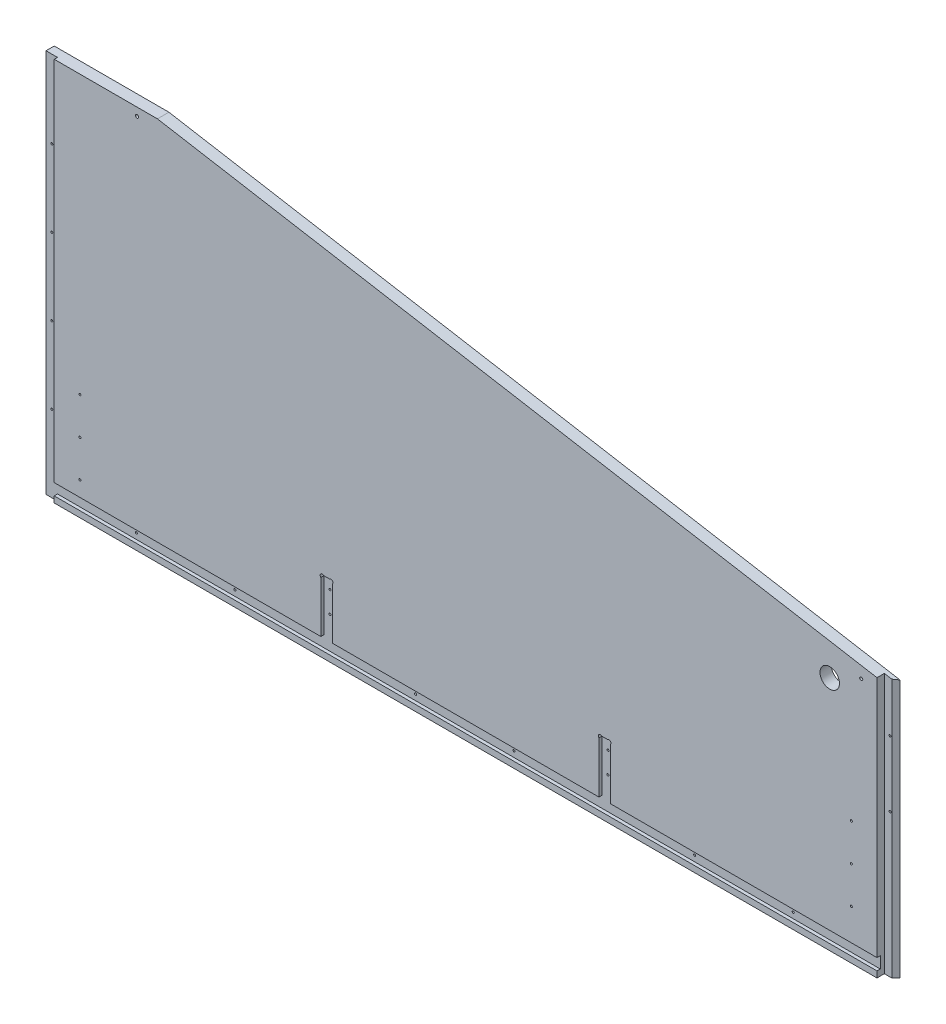
SolidWorks part; units mm, degrees
material "Maple"
ref_plane "Front Plane" through (0, 0, 0) normal (0, 0, 1) x (1, 0, 0)
ref_plane "Top Plane" through (0, 0, 0) normal (0, 1, 0) x (1, 0, 0)
ref_plane "Right Plane" through (0, 0, 0) normal (1, 0, 0) x (0, 0, -1)
sketch "Sketch1" plane through (0, 0, 0) normal (0, 0, 1) x (1, 0, 0)
  line L0 (8932.6508, -5243.5125) -> (10226.1458, -5243.5125)
  line L1 (9086.3208, -4722.0918) -> (10222.9708, -4853.7812)
  line L2 (8914.8708, -6342.0625) -> (10197.5708, -6342.0625)
  line L3 (8914.8708, -5808.6625) -> (10197.5708, -5808.6625)
  line L4 (8919.6333, -5253.0375) -> (10218.2083, -5253.0375)
  line L5 (9134.2633, -4656.1375) -> (9134.2633, -4638.3575)
  line L6 (9091.0833, -4638.3575) -> (9134.2633, -4638.3575)
  line L7 (9091.0833, -4567.2375) -> (9091.0833, -4638.3575)
  line L8 (9134.2633, -4656.1375) -> (9581.3033, -4656.1375)
  line L9 (9091.0833, -4567.2375) -> (9624.4833, -4567.2375)
  line L10 (9581.3033, -4656.1375) -> (9581.3033, -4638.3575)
  line L11 (9581.3033, -4638.3575) -> (9624.4833, -4638.3575)
  line L12 (9624.4833, -4567.2375) -> (9624.4833, -4638.3575)
  line L13 (8932.6508, -5225.7325) -> (9344.9775, -5225.7325)
  line L14 (8932.6508, -5256.2125) -> (8932.6508, -5243.5125)
  line L15 (8911.6958, -5256.2125) -> (8932.6508, -5256.2125)
  line L16 (8914.8708, -4722.0918) -> (9086.3208, -4722.0918)
  line L17 (8911.6958, -4715.5913) -> (8932.6508, -4715.5913)
  line L18 (8914.8708, -6342.0625) -> (8914.8708, -5808.6625)
  line L19 (12082.9917, -4722.0918) -> (10946.3417, -4853.7812)
  line L20 (12236.6617, -5243.5125) -> (10943.1667, -5243.5125)
  line L21 (10951.1042, -5253.0375) -> (12249.6792, -5253.0375)
  line L22 (10838.3917, -5656.2625) -> (11308.2917, -5656.2625)
  line L23 (10838.3917, -5719.7625) -> (11308.2917, -5719.7625)
  line L24 (10838.3917, -5742.5368) -> (11308.2917, -5742.5368)
  line L25 (10806.6417, -6342.0625) -> (11340.0417, -6342.0625)
  line L26 (10803.4667, -6335.7125) -> (11343.2167, -6335.7125)
  line L27 (10803.4667, -6317.9325) -> (11343.2167, -6317.9325)
  line L28 (10943.1667, -5225.7325) -> (11376.4483, -5225.7325)
  line L29 (11506.7292, -4754.5625) -> (10806.6417, -4827.5875)
  line L30 (11506.7292, -4567.2375) -> (11506.7292, -4754.5625)
  line L31 (10806.6417, -4567.2375) -> (10806.6417, -4827.5875)
  line L32 (10806.6417, -4567.2375) -> (11506.7292, -4567.2375)
  line L33 (10235.6708, -6329.3625) -> (10245.1958, -6329.3625)
  line L34 (10245.1958, -6329.3625) -> (10254.7208, -6278.5625)
  line L35 (10302.3458, -6329.3625) -> (10311.8708, -6278.5625)
  line L36 (10302.3458, -6329.3625) -> (10292.8208, -6329.3625)
  line L37 (10245.1958, -5821.3625) -> (10254.7208, -5872.1625)
  line L38 (10235.6708, -5821.3625) -> (10245.1958, -5821.3625)
  line L39 (10292.8208, -5821.3625) -> (10302.3458, -5821.3625)
  line L40 (10302.3458, -5821.3625) -> (10311.8708, -5872.1625)
  line L41 (10235.6708, -5821.3625) -> (10235.6708, -6329.3625)
  line L42 (10254.7208, -5872.1625) -> (10254.7208, -6278.5625)
  line L43 (10311.8708, -5872.1625) -> (10311.8708, -6278.5625)
  line L44 (10292.8208, -5821.3625) -> (10292.8208, -6329.3625)
  line L45 (8932.6508, -5225.7325) -> (8932.6508, -4715.5913)
  line L46 (8911.6958, -4715.5913) -> (8911.6958, -5256.2125)
  line L47 (8914.8708, -5248.275) -> (8914.8708, -4722.0918)
  line L48 (8919.6333, -5253.0375) -> (8914.8708, -5248.275)
  line L49 (8914.8708, -5145.0875) -> (8937.426, -5145.0875)
  line L50 (8914.8708, -5202.2375) -> (8937.426, -5202.2375)
  line L51 (10838.3917, -5656.2625) -> (10838.3917, -5719.7625)
  line L52 (10832.0417, -5736.1868) -> (10856.1717, -5736.1868)
  line L53 (10806.6417, -6342.0625) -> (10806.6417, -5818.7368)
  line L54 (10832.0417, -5649.9125) -> (10856.1717, -5649.9125)
  line L55 (10832.0417, -5726.1125) -> (10856.1717, -5726.1125)
  line L56 (10806.6417, -5818.7368) -> (10833.9015, -5818.7368)
  line L57 (10832.0417, -5806.0442) -> (10851.6815, -5806.0442)
  line L58 (10856.1717, -5801.5541) -> (10856.1717, -5736.1868)
  line L59 (10838.3917, -5814.2467) -> (10838.3917, -5742.5368)
  line L60 (10832.0417, -5806.0442) -> (10832.0417, -5736.1868)
  line L61 (10803.4667, -6317.9325) -> (10803.4667, -6335.7125)
  line L62 (10197.5708, -5808.6625) -> (10197.5708, -6342.0625)
  line L63 (9762.3842, -6348.4125) -> (9762.3842, -5802.3125)
  line L64 (9780.1642, -6348.4125) -> (9762.3842, -6348.4125)
  line L65 (9780.1642, -5802.3125) -> (9780.1642, -6348.4125)
  line L66 (9762.3842, -5802.3125) -> (9780.1642, -5802.3125)
  line L67 (9332.2775, -6348.4125) -> (9332.2775, -5802.3125)
  line L68 (9332.2775, -6348.4125) -> (9350.0575, -6348.4125)
  line L69 (9350.0575, -5802.3125) -> (9350.0575, -6348.4125)
  line L70 (9332.2775, -5802.3125) -> (9350.0575, -5802.3125)
  line L71 (9993.8374, -6061.075) -> (9993.8374, -6045.2418)
  line L72 (9998.5999, -6065.8375) -> (10014.4331, -6065.8375)
  line L73 (9998.5999, -6084.8875) -> (10014.4331, -6084.8875)
  line L74 (9993.8374, -6105.4832) -> (9993.8374, -6089.65)
  line L75 (9974.7874, -6105.4832) -> (9974.7874, -6089.65)
  line L76 (9954.1917, -6084.8875) -> (9970.0249, -6084.8875)
  line L77 (9974.7874, -6061.075) -> (9974.7874, -6045.2418)
  line L78 (9954.1917, -6065.8375) -> (9970.0249, -6065.8375)
  line L79 (10793.9417, -6237.2875) -> (10816.4969, -6237.2875)
  line L80 (10793.9417, -6294.4375) -> (10816.4969, -6294.4375)
  line L81 (10856.1717, -5649.9125) -> (10856.1717, -5726.1125)
  line L82 (10832.0417, -5726.1125) -> (10832.0417, -5649.9125)
  line L83 (10226.1458, -5225.7325) -> (10226.1458, -5243.5125)
  line L84 (10205.1908, -5257.8) -> (10205.1908, -4844.2499)
  line L85 (10230.9083, -4844.2499) -> (10230.9083, -5257.8)
  line L86 (10205.1908, -5257.8) -> (10230.9083, -5257.8)
  line L87 (10205.1908, -4844.2499) -> (10230.9083, -4844.2499)
  line L88 (10946.3417, -5176.8375) -> (10968.8969, -5176.8375)
  line L89 (9349.4676, -5141.9125) -> (9358.2674, -5141.9125)
  line L90 (10946.3417, -5119.6875) -> (10968.8969, -5119.6875)
  line L91 (9929.011, -4660.9635) -> (10066.0807, -4660.9635)
  line L92 (9929.011, -4678.7435) -> (10066.0807, -4678.7435)
  line L93 (10943.1667, -5225.7325) -> (10943.1667, -5243.5125)
  line L94 (10946.3417, -5248.275) -> (10951.1042, -5253.0375)
  line L95 (10946.3417, -5257.8063) -> (10946.3417, -4849.0188)
  line L96 (10964.1217, -5257.8) -> (10964.1217, -4844.2499)
  line L97 (10938.4042, -4844.2499) -> (10938.4042, -5257.8)
  line L98 (10938.4042, -5257.8) -> (10964.1217, -5257.8)
  line L99 (10964.1217, -4844.2499) -> (10938.4042, -4844.2499)
  line L100 (10344.8908, -4560.8875) -> (10369.0208, -4560.8875)
  line L101 (10344.8908, -4560.8875) -> (10369.0208, -4560.8875)
  line L102 (10800.2917, -4560.8875) -> (10824.4217, -4560.8875)
  line L103 (10200.4156, -5119.6875) -> (10222.9708, -5119.6875)
  line L104 (10200.4156, -5176.8375) -> (10222.9708, -5176.8375)
  line L105 (9344.9775, -5146.4026) -> (9344.9775, -5225.7325)
  line L106 (10344.8908, -4560.8875) -> (10344.8908, -4833.9375)
  line L107 (9792.8642, -5225.7325) -> (9792.8642, -5146.4026)
  line L108 (9362.7575, -5225.7325) -> (9775.0842, -5225.7325)
  line L109 (9680.3633, -4761.8396) -> (9680.3633, -4559.9604)
  line L110 (9656.2333, -4559.9604) -> (9680.3633, -4559.9604)
  line L111 (9656.2333, -4761.8396) -> (9680.3633, -4761.8396)
  line L112 (9656.2333, -4761.8396) -> (9656.2333, -4559.9604)
  line L113 (9779.5743, -5141.9125) -> (9788.374, -5141.9125)
  line L114 (10070.5708, -4665.4536) -> (10070.5708, -4674.2534)
  line L115 (9924.5208, -4674.2534) -> (9924.5208, -4665.4536)
  line L116 (12127.4417, -6188.3925) -> (12205.5015, -6188.3925)
  line L117 (12209.9917, -6170.6125) -> (12209.9917, -6183.9024)
  line L118 (9792.8642, -5225.7325) -> (10226.1458, -5225.7325)
  line L119 (9662.5833, -4754.5625) -> (10362.6708, -4827.5875)
  line L120 (9662.5833, -4567.2375) -> (9662.5833, -4754.5625)
  line L121 (10362.6708, -4567.2375) -> (10362.6708, -4827.5875)
  line L122 (9662.5833, -4567.2375) -> (10362.6708, -4567.2375)
  line L123 (10824.4217, -4833.9375) -> (10800.2917, -4833.9375)
  line L124 (10800.2917, -4833.9375) -> (10800.2917, -4560.8875)
  line L125 (10824.4217, -4560.8875) -> (10824.4217, -4833.9375)
  line L126 (10344.8908, -4833.9375) -> (10369.0208, -4833.9375)
  line L127 (10369.0208, -4833.9375) -> (10369.0208, -4560.8875)
  line L128 (10222.9708, -5248.275) -> (10218.2083, -5253.0375)
  line L129 (10222.9708, -5257.8063) -> (10222.9708, -4849.0188)
  line L130 (11734.6544, -5701.375) -> (11739.2301, -5701.375)
  line L131 (9362.7575, -5225.7325) -> (9362.7575, -5146.4026)
  line L132 (9775.0842, -5146.4026) -> (9775.0842, -5225.7325)
  line L133 (11761.3864, -5701.375) -> (11756.8282, -5701.375)
  line L134 (11734.6544, -5693.755) -> (11739.2301, -5693.755)
  line L135 (11761.4039, -5693.755) -> (11756.8282, -5693.755)
  line L136 (11734.6544, -5701.375) -> (11739.2301, -5701.375)
  line L137 (11744.3462, -5721.3024) -> (11744.3462, -5706.4179)
  line L138 (11751.7122, -5721.3024) -> (11751.7122, -5706.4179)
  line L139 (11740.0917, -6170.6125) -> (11740.0917, -6183.9024)
  line L140 (11689.2917, -6188.3925) -> (11822.6417, -6188.3925)
  line L141 (11689.2917, -6348.4093) -> (11689.2917, -6164.2657)
  line L142 (11689.2917, -6164.2657) -> (11746.4417, -6164.2657)
  line L143 (11746.4417, -6164.2657) -> (11746.4417, -6188.3925)
  line L144 (11689.2917, -6164.2657) -> (11746.4417, -6164.2657)
  line L145 (11340.0417, -5818.7368) -> (11340.0417, -6342.0625)
  line L146 (11290.5117, -5726.1125) -> (11314.6417, -5726.1125)
  line L147 (11290.5117, -5649.9125) -> (11290.5117, -5726.1125)
  line L148 (11340.0417, -5818.7368) -> (11312.7818, -5818.7368)
  line L149 (11314.6417, -5806.0442) -> (11295.0018, -5806.0442)
  line L150 (11290.5117, -5801.5541) -> (11290.5117, -5736.1868)
  line L151 (11308.2917, -5814.2467) -> (11308.2917, -5742.5368)
  line L152 (11314.6417, -5806.0442) -> (11314.6417, -5736.1868)
  line L153 (11290.5117, -5736.1868) -> (11314.6417, -5736.1868)
  line L154 (11848.0417, -6267.1325) -> (11962.3417, -6267.1325)
  line L155 (11962.3417, -6267.1325) -> (11962.3417, -6203.6325)
  line L156 (11343.2167, -6317.9325) -> (11343.2167, -6335.7125)
  line L157 (11365.4417, -5656.2625) -> (11365.4417, -5719.7625)
  line L158 (11365.4417, -5656.2625) -> (11479.7417, -5656.2625)
  line L159 (11778.1917, -6071.3937) -> (11802.3217, -6071.3937)
  line L160 (11314.6417, -5726.1125) -> (11314.6417, -5649.9125)
  line L161 (11314.6417, -5649.9125) -> (11290.5117, -5649.9125)
  line L162 (11308.2917, -5719.7625) -> (11308.2917, -5656.2625)
  line L163 (11689.2917, -6348.4093) -> (11713.4217, -6348.4093)
  line L164 (12203.6417, -6164.2657) -> (12260.7917, -6164.2657)
  line L165 (11713.4217, -6348.4093) -> (11713.4217, -6164.2657)
  line L166 (11695.6417, -6342.0625) -> (11695.6417, -6170.6125)
  line L167 (11695.6417, -6048.5337) -> (11699.4517, -6052.3437)
  line L168 (11822.6417, -6292.5325) -> (11822.6417, -6188.3925)
  line L169 (11695.6417, -6342.0625) -> (11695.6417, -6170.6125)
  line L170 (11848.0417, -6203.6325) -> (11962.3417, -6203.6325)
  line L171 (11848.0417, -6203.6325) -> (11848.0417, -6267.1325)
  line L172 (11987.7417, -6267.1325) -> (11987.7417, -6203.6325)
  line L173 (11784.5417, -6077.7437) -> (11784.5417, -6141.2438)
  line L174 (11517.8417, -5656.2625) -> (11632.1417, -5656.2625)
  line L175 (11632.1417, -5656.2625) -> (11632.1417, -5719.7625)
  line L176 (11632.1417, -5719.7625) -> (11517.8417, -5719.7625)
  line L177 (11517.8417, -5719.7625) -> (11517.8417, -5656.2625)
  line L178 (11692.4667, -6028.2137) -> (11692.4667, -6045.9937)
  line L179 (11695.6417, -5979.3188) -> (11718.1969, -5979.3188)
  line L180 (11695.6417, -5922.1687) -> (11718.1969, -5922.1687)
  line L181 (11821.0415, -5722.9375) -> (11821.0415, -5943.6)
  line L182 (11687.7042, -5651.5) -> (11701.9917, -5651.5)
  line L183 (11687.7042, -5651.5) -> (11687.7042, -6055.5251)
  line L184 (11687.7042, -6055.5251) -> (11701.9917, -6055.5251)
  line L185 (11701.9917, -6055.5251) -> (11701.9917, -5651.5)
  line L186 (11695.6417, -6055.2013) -> (11695.6417, -5649.595)
  line L187 (11695.6417, -5656.2625) -> (11695.6417, -6048.5337)
  line L188 (11695.6417, -6170.6125) -> (11740.0917, -6170.6125)
  line L189 (12203.6417, -6164.2657) -> (12203.6417, -6188.3925)
  line L190 (12254.4417, -6342.0625) -> (12254.4417, -6170.6125)
  line L191 (12129.0419, -5943.6) -> (12129.0419, -5722.9375)
  line L192 (12254.4417, -6048.5337) -> (12250.6317, -6052.3437)
  line L193 (12257.6167, -6045.9937) -> (12257.6167, -6028.2137)
  line L194 (12248.0917, -5651.5) -> (12262.3792, -5651.5)
  line L195 (12262.3792, -5651.5) -> (12262.3792, -6055.5251)
  line L196 (12262.3792, -6055.5251) -> (12248.0917, -6055.5251)
  line L197 (12248.0917, -6055.5251) -> (12248.0917, -5651.5)
  line L198 (12254.4417, -6141.2438) -> (12254.4417, -6077.7437)
  line L199 (12236.6617, -6164.2657) -> (12260.7917, -6164.2657)
  line L200 (12102.0417, -6267.1325) -> (11987.7417, -6267.1325)
  line L201 (11330.1865, -6237.2875) -> (11352.7417, -6237.2875)
  line L202 (11330.1865, -6294.4375) -> (11352.7417, -6294.4375)
  line L203 (11474.6617, -5851.8425) -> (11492.4417, -5851.8425)
  line L204 (11474.6617, -5808.6625) -> (11474.6617, -5851.8425)
  line L205 (11403.5417, -5808.6625) -> (11474.6617, -5808.6625)
  line L206 (11492.4417, -5851.8425) -> (11492.4417, -6298.8825)
  line L207 (11403.5417, -6342.0625) -> (11403.5417, -5808.6625)
  line L208 (11474.6617, -6298.8825) -> (11492.4417, -6298.8825)
  line L209 (11474.6617, -6342.0625) -> (11474.6617, -6298.8825)
  line L210 (11403.5417, -6342.0625) -> (11474.6617, -6342.0625)
  line L211 (11619.4417, -5851.8425) -> (11601.6617, -5851.8425)
  line L212 (11601.6617, -5808.6625) -> (11601.6617, -5851.8425)
  line L213 (11530.5417, -5808.6625) -> (11601.6617, -5808.6625)
  line L214 (11619.4417, -5851.8425) -> (11619.4417, -6298.8825)
  line L215 (11530.5417, -6342.0625) -> (11530.5417, -5808.6625)
  line L216 (11619.4417, -6298.8825) -> (11601.6617, -6298.8825)
  line L217 (11601.6617, -6342.0625) -> (11601.6617, -6298.8825)
  line L218 (11530.5417, -6342.0625) -> (11601.6617, -6342.0625)
  line L219 (11479.7417, -5719.7625) -> (11479.7417, -5656.2625)
  line L220 (11365.4417, -5719.7625) -> (11479.7417, -5719.7625)
  line L221 (11778.1917, -6147.5937) -> (11802.3217, -6147.5937)
  line L222 (11802.3217, -6071.3937) -> (11802.3217, -6147.5937)
  line L223 (11778.1917, -6147.5937) -> (11778.1917, -6071.3937)
  line L224 (12254.4417, -5922.1687) -> (12231.8865, -5922.1687)
  line L225 (12254.4417, -5979.3188) -> (12231.8865, -5979.3188)
  line L226 (12254.4417, -6055.2013) -> (12254.4417, -5649.595)
  line L227 (12254.4417, -6048.5337) -> (12254.4417, -5656.2625)
  line L228 (11841.6917, -5702.2873) -> (12108.3917, -5702.2873)
  line L229 (11822.6417, -6292.5325) -> (12127.4417, -6292.5325)
  line L230 (12127.4417, -6292.5325) -> (12127.4417, -6188.3925)
  line L231 (12254.4417, -6170.6125) -> (12209.9917, -6170.6125)
  line L232 (11695.6417, -6342.0625) -> (12254.4417, -6342.0625)
  line L233 (12236.6617, -6348.4093) -> (12260.7917, -6348.4093)
  line L234 (12260.7917, -6348.4093) -> (12260.7917, -6164.2657)
  line L235 (12236.6617, -6348.4093) -> (12236.6617, -6164.2657)
  line L236 (12102.0417, -6203.6325) -> (12102.0417, -6267.1325)
  line L237 (11987.7417, -6203.6325) -> (12102.0417, -6203.6325)
  line L238 (12236.6617, -6147.5937) -> (12236.6617, -6071.3937)
  line L239 (12203.6417, -6188.3925) -> (12260.7917, -6188.3925)
  line L240 (11098.7417, -4665.4536) -> (11098.7417, -4674.2534)
  line L241 (11394.2283, -5146.4026) -> (11394.2283, -5225.7325)
  line L242 (11376.4483, -5225.7325) -> (11376.4483, -5146.4026)
  line L243 (11394.2283, -5225.7325) -> (11806.555, -5225.7325)
  line L244 (11841.6917, -5964.2502) -> (12108.3917, -5964.2502)
  line L245 (12236.6617, -6147.5937) -> (12260.7917, -6147.5937)
  line L246 (12236.6617, -5256.2125) -> (12236.6617, -5243.5125)
  line L247 (12260.7917, -6147.5937) -> (12260.7917, -6071.3937)
  line L248 (12260.7917, -6071.3937) -> (12236.6617, -6071.3937)
  line L249 (12254.4417, -6077.7437) -> (11784.5417, -6077.7437)
  line L250 (11784.5417, -6141.2438) -> (12254.4417, -6141.2438)
  line L252 (12254.4417, -5656.2625) -> (11695.6417, -5656.2625)
  line L253 (11699.4517, -6052.3437) -> (12250.6317, -6052.3437)
  line L254 (11692.4667, -6045.9937) -> (12257.6167, -6045.9937)
  line L255 (11692.4667, -6028.2137) -> (12257.6167, -6028.2137)
  line L256 (11824.335, -5146.4026) -> (11824.335, -5225.7325)
  line L257 (11811.0451, -5141.9125) -> (11819.8449, -5141.9125)
  line L258 (11244.7917, -4674.2534) -> (11244.7917, -4665.4536)
  line L259 (11806.555, -5225.7325) -> (11806.555, -5146.4026)
  line L260 (11488.9492, -4761.8396) -> (11488.9492, -4559.9604)
  line L261 (11488.9492, -4559.9604) -> (11513.0792, -4559.9604)
  line L262 (11488.9492, -4761.8396) -> (11513.0792, -4761.8396)
  line L263 (11513.0792, -4761.8396) -> (11513.0792, -4559.9604)
  line L264 (11240.3015, -4660.9635) -> (11103.2318, -4660.9635)
  line L265 (11103.2318, -4678.7435) -> (11240.3015, -4678.7435)
  line L266 (12236.6617, -5225.7325) -> (12236.6617, -4715.5913)
  line L267 (12257.6167, -4715.5913) -> (12257.6167, -5256.2125)
  line L268 (12254.4417, -5248.275) -> (12254.4417, -4722.0918)
  line L269 (12236.6617, -5225.7325) -> (11824.335, -5225.7325)
  line L270 (12035.0492, -4656.1375) -> (12035.0492, -4638.3575)
  line L271 (12078.2292, -4638.3575) -> (12035.0492, -4638.3575)
  line L272 (12078.2292, -4567.2375) -> (12078.2292, -4638.3575)
  line L273 (12035.0492, -4656.1375) -> (11588.0092, -4656.1375)
  line L274 (11544.8292, -4567.2375) -> (12078.2292, -4567.2375)
  line L275 (11588.0092, -4656.1375) -> (11588.0092, -4638.3575)
  line L276 (11544.8292, -4638.3575) -> (11588.0092, -4638.3575)
  line L277 (11544.8292, -4567.2375) -> (11544.8292, -4638.3575)
  line L278 (12249.6792, -5253.0375) -> (12254.4417, -5248.275)
  line L280 (12257.6167, -5256.2125) -> (12236.6617, -5256.2125)
  line L281 (12231.8865, -5145.0875) -> (12254.4417, -5145.0875)
  line L282 (12231.8865, -5202.2375) -> (12254.4417, -5202.2375)
  line L283 (12236.6617, -4715.5913) -> (12257.6167, -4715.5913)
  line L284 (12082.9917, -4722.0918) -> (12254.4417, -4722.0918)
  line L285 (11380.9385, -5141.9125) -> (11389.7382, -5141.9125)
  circle A0 centre (8923.7608, -4778.9042) radius 1.5875
  circle A1 centre (9062.6598, -4736.3765) radius 2.3685
  circle A2 centre (9051.3958, -6281.7375) radius 22.225
  circle A3 centre (9083.1458, -6249.9875) radius 1.5875
  circle A4 centre (9083.1458, -6313.4875) radius 1.5875
  circle A5 centre (9019.6458, -6249.9875) radius 1.5875
  circle A6 centre (9019.6458, -6313.4875) radius 1.5875
  circle A7 centre (8972.3383, -5202.2375) radius 1.5875
  circle A8 centre (8923.7608, -5015.9708) radius 1.5875
  circle A9 centre (8923.7608, -5134.5042) radius 1.5875
  circle A10 centre (9054.5708, -5234.6225) radius 1.5875
  circle A11 centre (8923.7608, -4897.4375) radius 1.5875
  circle A12 centre (8972.3383, -5087.9375) radius 1.5875
  circle A13 centre (8972.3383, -5145.0875) radius 1.5875
  circle A14 centre (10847.2817, -5668.9625) radius 1.5875
  circle A15 centre (10847.2817, -5707.0625) radius 1.5875
  circle A16 centre (10847.2817, -5755.2368) radius 1.5875
  circle A17 centre (10851.4092, -6237.2875) radius 1.5875
  circle A18 centre (10851.4092, -6294.4375) radius 1.5875
  circle A19 centre (10847.2817, -5793.3442) radius 1.5875
  arc A20 (10833.9015, -5818.7368) -> (10838.3917, -5814.2467) centre (10836.1466, -5816.4918) ccw
  arc A21 (10851.6815, -5806.0442) -> (10856.1717, -5801.5541) centre (10853.9266, -5803.7992) ccw
  circle A22 centre (10882.8417, -6040.4375) radius 1.5875
  circle A23 centre (10882.8417, -6218.2375) radius 1.5875
  circle A24 centre (10882.8417, -5862.6375) radius 1.5875
  circle A25 centre (10908.2417, -6326.8225) radius 1.5875
  circle A26 centre (10908.2417, -6326.8225) radius 1.5875
  circle A27 centre (10851.4092, -6180.1375) radius 1.5875
  circle A28 centre (10815.5317, -4783.4231) radius 1.5875
  circle A29 centre (10815.5317, -4696.9488) radius 1.5875
  circle A30 centre (10815.5317, -4610.4746) radius 1.5875
  circle A31 centre (10979.1323, -4867.0082) radius 2.3685
  circle A32 centre (10190.1802, -4867.0082) radius 2.3685
  circle A33 centre (10955.2317, -4929.9812) radius 1.5875
  circle A34 centre (10955.2317, -5031.5812) radius 1.5875
  circle A35 centre (10214.0808, -4929.9812) radius 1.5875
  circle A36 centre (10214.0808, -5031.5812) radius 1.5875
  circle A37 centre (9341.1675, -6265.8625) radius 1.5875
  circle A38 centre (9771.2742, -5884.8625) radius 1.5875
  circle A39 centre (9771.2742, -6138.8625) radius 1.5875
  circle A40 centre (9771.2742, -6011.8625) radius 1.5875
  arc A41 (10036.2287, -6113.8083) -> (10051.3426, -6111.6033) centre (10042.9639, -6107.0732) ccw
  arc A42 (10051.3426, -6111.6033) -> (10051.3426, -6039.1217) centre (9984.3124, -6075.3625) ccw
  arc A43 (10051.3426, -6039.1217) -> (10036.2287, -6036.9167) centre (10042.9639, -6043.6518) ccw
  arc A44 (10034.5851, -6102.5431) -> (10034.5851, -6048.1819) centre (9984.3124, -6075.3625) ccw
  arc A45 (10034.5851, -6102.5431) -> (10036.2287, -6113.8083) centre (10042.9639, -6107.0732) ccw
  arc A46 (10036.2287, -6036.9167) -> (10034.5851, -6048.1819) centre (10042.9639, -6043.6518) ccw
  arc A47 (9945.8666, -6127.2787) -> (9948.0717, -6142.3927) centre (9952.6018, -6134.0139) ccw
  arc A48 (9948.0717, -6142.3927) -> (10020.5532, -6142.3927) centre (9984.3124, -6075.3625) ccw
  arc A49 (10020.5532, -6142.3927) -> (10022.7583, -6127.2787) centre (10016.0231, -6134.0139) ccw
  arc A50 (9957.1319, -6125.6352) -> (10011.493, -6125.6352) centre (9984.3124, -6075.3625) ccw
  arc A51 (9957.1319, -6125.6352) -> (9945.8666, -6127.2787) centre (9952.6018, -6134.0139) ccw
  arc A52 (10022.7583, -6127.2787) -> (10011.493, -6125.6352) centre (10016.0231, -6134.0139) ccw
  arc A53 (9932.3962, -6036.9167) -> (9917.2822, -6039.1217) centre (9925.661, -6043.6518) ccw
  arc A54 (9917.2822, -6039.1217) -> (9917.2822, -6111.6033) centre (9984.3124, -6075.3625) ccw
  arc A55 (9917.2822, -6111.6033) -> (9932.3962, -6113.8083) centre (9925.661, -6107.0732) ccw
  arc A56 (9934.0398, -6048.1819) -> (9934.0398, -6102.5431) centre (9984.3124, -6075.3625) ccw
  arc A57 (9934.0398, -6048.1819) -> (9932.3962, -6036.9167) centre (9925.661, -6043.6518) ccw
  arc A58 (9932.3962, -6113.8083) -> (9934.0398, -6102.5431) centre (9925.661, -6107.0732) ccw
  arc A59 (9945.8666, -6023.4463) -> (9957.1319, -6025.0898) centre (9952.6018, -6016.7111) ccw
  arc A60 (10011.493, -6025.0898) -> (10022.7583, -6023.4463) centre (10016.0231, -6016.7111) ccw
  arc A61 (10011.493, -6025.0898) -> (9957.1319, -6025.0898) centre (9984.3124, -6075.3625) ccw
  arc A62 (9948.0717, -6008.3323) -> (9945.8666, -6023.4463) centre (9952.6018, -6016.7111) ccw
  arc A63 (10020.5532, -6008.3323) -> (9948.0717, -6008.3323) centre (9984.3124, -6075.3625) ccw
  arc A64 (10022.7583, -6023.4463) -> (10020.5532, -6008.3323) centre (10016.0231, -6016.7111) ccw
  arc A65 (10005.0943, -6187.7574) -> (10096.7073, -6096.1443) centre (9984.3124, -6075.3625) ccw
  arc A66 (9993.8374, -6178.3911) -> (10005.0943, -6187.7574) centre (10003.3624, -6178.3911) ccw
  arc A67 (10001.6306, -6169.0249) -> (10077.9748, -6092.6807) centre (9984.3124, -6075.3625) ccw
  arc A68 (10087.3411, -6084.8875) -> (10077.9748, -6092.6807) centre (10087.3411, -6094.4125) ccw
  arc A69 (10001.6306, -6169.0249) -> (9993.8374, -6178.3911) centre (10003.3624, -6178.3911) ccw
  arc A70 (9963.5306, -6187.7574) -> (9974.7874, -6178.3911) centre (9965.2624, -6178.3911) ccw
  arc A71 (9871.9176, -6096.1443) -> (9963.5306, -6187.7574) centre (9984.3124, -6075.3625) ccw
  arc A72 (9881.2838, -6084.8875) -> (9871.9176, -6096.1443) centre (9881.2838, -6094.4125) ccw
  arc A73 (9890.65, -6092.6807) -> (9966.9943, -6169.0249) centre (9984.3124, -6075.3625) ccw
  arc A74 (9974.7874, -6178.3911) -> (9966.9943, -6169.0249) centre (9965.2624, -6178.3911) ccw
  arc A75 (9890.65, -6092.6807) -> (9881.2838, -6084.8875) centre (9881.2838, -6094.4125) ccw
  arc A76 (9871.9176, -6054.5807) -> (9881.2838, -6065.8375) centre (9881.2838, -6056.3125) ccw
  arc A77 (9963.5306, -5962.9676) -> (9871.9176, -6054.5807) centre (9984.3124, -6075.3625) ccw
  arc A78 (9974.7874, -5972.3339) -> (9963.5306, -5962.9676) centre (9965.2624, -5972.3339) ccw
  arc A79 (9966.9943, -5981.7001) -> (9890.65, -6058.0443) centre (9984.3124, -6075.3625) ccw
  arc A80 (9881.2838, -6065.8375) -> (9890.65, -6058.0443) centre (9881.2838, -6056.3125) ccw
  arc A81 (9966.9943, -5981.7001) -> (9974.7874, -5972.3339) centre (9965.2624, -5972.3339) ccw
  arc A82 (10077.9748, -6058.0443) -> (10087.3411, -6065.8375) centre (10087.3411, -6056.3125) ccw
  arc A83 (9993.8374, -5972.3339) -> (10001.6306, -5981.7001) centre (10003.3624, -5972.3339) ccw
  arc A84 (10077.9748, -6058.0443) -> (10001.6306, -5981.7001) centre (9984.3124, -6075.3625) ccw
  arc A85 (10087.3411, -6065.8375) -> (10096.7073, -6054.5807) centre (10087.3411, -6056.3125) ccw
  arc A86 (10096.7073, -6054.5807) -> (10005.0943, -5962.9676) centre (9984.3124, -6075.3625) ccw
  arc A87 (10005.0943, -5962.9676) -> (9993.8374, -5972.3339) centre (10003.3624, -5972.3339) ccw
  arc A88 (10014.4331, -6065.8375) -> (10018.7361, -6059.0339) centre (10014.4331, -6061.075) ccw
  arc A89 (10018.7361, -6059.0339) -> (10000.641, -6040.9388) centre (9984.3124, -6075.3625) ccw
  arc A90 (10000.641, -6040.9388) -> (9993.8374, -6045.2418) centre (9998.5999, -6045.2418) ccw
  arc A91 (9993.8374, -6061.075) -> (9998.5999, -6065.8375) centre (9998.5999, -6061.075) ccw
  arc A92 (9993.8374, -6105.4832) -> (10000.641, -6109.7862) centre (9998.5999, -6105.4832) ccw
  arc A93 (10000.641, -6109.7862) -> (10018.7361, -6091.6911) centre (9984.3124, -6075.3625) ccw
  arc A94 (10018.7361, -6091.6911) -> (10014.4331, -6084.8875) centre (10014.4331, -6089.65) ccw
  arc A95 (9998.5999, -6084.8875) -> (9993.8374, -6089.65) centre (9998.5999, -6089.65) ccw
  arc A96 (9954.1917, -6084.8875) -> (9949.8888, -6091.6911) centre (9954.1917, -6089.65) ccw
  arc A97 (9949.8888, -6091.6911) -> (9967.9839, -6109.7862) centre (9984.3124, -6075.3625) ccw
  arc A98 (9967.9839, -6109.7862) -> (9974.7874, -6105.4832) centre (9970.0249, -6105.4832) ccw
  arc A99 (9974.7874, -6089.65) -> (9970.0249, -6084.8875) centre (9970.0249, -6089.65) ccw
  arc A100 (9970.0249, -6065.8375) -> (9974.7874, -6061.075) centre (9970.0249, -6061.075) ccw
  arc A101 (9949.8888, -6059.0339) -> (9954.1917, -6065.8375) centre (9954.1917, -6061.075) ccw
  arc A102 (9967.9839, -6040.9388) -> (9949.8888, -6059.0339) centre (9984.3124, -6075.3625) ccw
  arc A103 (9974.7874, -6045.2418) -> (9967.9839, -6040.9388) centre (9970.0249, -6045.2418) ccw
  arc A104 (10096.7073, -6096.1443) -> (10087.3411, -6084.8875) centre (10087.3411, -6094.4125) ccw
  circle A105 centre (9771.2742, -6265.8625) radius 1.5875
  circle A106 centre (9341.1675, -5884.8625) radius 1.5875
  circle A107 centre (9341.1675, -6138.8625) radius 1.5875
  circle A108 centre (9341.1675, -6011.8625) radius 1.5875
  circle A109 centre (11037.2315, -4887.5494) radius 15.0812
  arc A110 (9349.4676, -5141.9125) -> (9344.9775, -5146.4026) centre (9347.2226, -5144.1576) ccw
  arc A111 (9362.7575, -5146.4026) -> (9358.2674, -5141.9125) centre (9360.5124, -5144.1576) ccw
  circle A112 centre (9946.7458, -4669.8535) radius 1.5875
  arc A113 (9924.5208, -4674.2534) -> (9929.011, -4678.7435) centre (9926.7659, -4676.4984) ccw
  circle A114 centre (11003.8092, -5176.8375) radius 1.5875
  circle A115 centre (11003.8092, -5119.6875) radius 1.5875
  circle A116 centre (10353.7808, -4696.9488) radius 1.5875
  circle A117 centre (10353.7808, -4610.4746) radius 1.5875
  circle A118 centre (10353.7808, -4783.4231) radius 1.5875
  circle A119 centre (11003.8092, -5062.5375) radius 1.5875
  circle A120 centre (9353.8675, -5160.9625) radius 1.5875
  circle A121 centre (9638.7708, -5234.6225) radius 1.5875
  circle A122 centre (9671.4733, -4724.1144) radius 1.5875
  circle A123 centre (9671.4733, -4661.3637) radius 1.5875
  circle A124 centre (9671.4733, -4598.6129) radius 1.5875
  arc A125 (9792.8642, -5146.4026) -> (9788.374, -5141.9125) centre (9790.6191, -5144.1576) ccw
  arc A126 (9779.5743, -5141.9125) -> (9775.0842, -5146.4026) centre (9777.3292, -5144.1576) ccw
  circle A127 centre (10048.3458, -4669.8535) radius 1.5875
  arc A128 (10070.5708, -4665.4536) -> (10066.0807, -4660.9635) centre (10068.3258, -4663.2086) ccw
  arc A129 (10066.0807, -4678.7435) -> (10070.5708, -4674.2534) centre (10068.3258, -4676.4984) ccw
  circle A130 centre (9997.5458, -4669.8535) radius 1.5875
  arc A131 (9929.011, -4660.9635) -> (9924.5208, -4665.4536) centre (9926.7659, -4663.2086) ccw
  circle A132 centre (10132.081, -4887.5494) radius 15.0812
  circle A133 centre (10165.5033, -5176.8375) radius 1.5875
  circle A134 centre (10165.5033, -5119.6875) radius 1.5875
  circle A135 centre (9486.3708, -5234.6225) radius 1.5875
  circle A136 centre (10165.5033, -5062.5375) radius 1.5875
  circle A137 centre (9206.9708, -5234.6225) radius 1.5875
  circle A138 centre (10070.5708, -5234.6225) radius 1.5875
  circle A139 centre (9918.1708, -5234.6225) radius 1.5875
  circle A140 centre (9783.9742, -5160.9625) radius 1.5875
  circle A141 centre (9783.9742, -5193.9825) radius 1.5875
  circle A142 centre (9353.8675, -5193.9825) radius 1.5875
  circle A143 centre (11073.3417, -6326.8225) radius 1.5875
  circle A144 centre (11073.3417, -6326.8225) radius 1.5875
  circle A145 centre (11295.2742, -6180.1375) radius 1.5875
  circle A146 centre (11295.2742, -6294.4375) radius 1.5875
  circle A147 centre (11295.2742, -6237.2875) radius 1.5875
  circle A148 centre (11975.0417, -5692.775) radius 3.4925
  circle A149 centre (11263.8417, -5862.6375) radius 1.5875
  arc A150 (11739.2301, -5701.375) -> (11744.3462, -5706.4179) centre (11748.0292, -5697.565) ccw
  arc A151 (11751.7122, -5706.4179) -> (11756.8282, -5701.375) centre (11748.0292, -5697.565) ccw
  arc A152 (11744.3462, -5721.3024) -> (11751.7122, -5721.3024) centre (11748.0292, -5725.505) ccw
  arc A153 (11734.6544, -5693.755) -> (11724.9787, -5697.565) centre (11730.5667, -5697.565) ccw
  arc A154 (11756.8282, -5693.755) -> (11739.2301, -5693.755) centre (11748.0292, -5697.565) ccw
  arc A155 (11724.9787, -5697.565) -> (11734.6544, -5701.375) centre (11730.5667, -5697.565) ccw
  arc A156 (11761.3864, -5701.375) -> (11771.0797, -5697.565) centre (11765.4842, -5697.565) ccw
  arc A157 (11771.0797, -5697.565) -> (11761.4039, -5693.755) centre (11765.4917, -5697.565) ccw
  arc A158 (11740.0917, -6183.9024) -> (11744.5818, -6188.3925) centre (11742.3367, -6186.1474) ccw
  arc A159 (12205.5015, -6188.3925) -> (12209.9917, -6183.9024) centre (12207.7466, -6186.1474) ccw
  circle A160 centre (11299.4017, -5793.3442) radius 1.5875
  arc A161 (11308.2917, -5814.2467) -> (11312.7818, -5818.7368) centre (11310.5367, -5816.4918) ccw
  arc A162 (11290.5117, -5801.5541) -> (11295.0018, -5806.0442) centre (11292.7567, -5803.7992) ccw
  circle A163 centre (11704.5317, -6314.149) radius 1.5875
  circle A164 centre (11748.9817, -6208.7125) radius 1.5875
  circle A165 centre (11263.8417, -6218.2375) radius 1.5875
  circle A166 centre (11263.8417, -6040.4375) radius 1.5875
  circle A167 centre (11238.4417, -6326.8225) radius 1.5875
  circle A168 centre (11238.4417, -6326.8225) radius 1.5875
  circle A169 centre (11299.4017, -5668.9625) radius 1.5875
  circle A170 centre (11299.4017, -5707.0625) radius 1.5875
  circle A171 centre (11726.7567, -6179.5025) radius 1.5875
  circle A172 centre (11704.5317, -6199.3198) radius 1.5875
  circle A173 centre (11748.9817, -6272.2125) radius 1.5875
  circle A174 centre (11704.5317, -6256.7344) radius 1.5875
  circle A175 centre (11299.4017, -5755.2368) radius 1.5875
  circle A176 centre (11913.4467, -6301.4225) radius 1.5875
  circle A177 centre (11790.2567, -6301.4225) radius 1.5875
  circle A178 centre (11793.4317, -6128.5437) radius 1.5875
  circle A179 centre (11753.1092, -5865.0188) radius 1.5875
  circle A180 centre (11809.9417, -6037.1038) radius 1.5875
  circle A181 centre (11809.9417, -6037.1038) radius 1.5875
  circle A182 centre (11753.1092, -5922.1687) radius 1.5875
  circle A183 centre (11975.0417, -5973.7625) radius 3.4925
  circle A184 centre (11975.0417, -6037.1038) radius 1.5875
  circle A185 centre (11753.1092, -5979.3188) radius 1.5875
  circle A186 centre (11975.0417, -6037.1038) radius 1.5875
  arc A187 (11841.6917, -5702.2873) -> (11821.0415, -5722.9375) centre (11841.6917, -5722.9375) ccw
  circle A188 centre (11811.5292, -5833.2687) radius 3.4925
  arc A189 (11821.0415, -5943.6) -> (11841.6917, -5964.2502) centre (11841.6917, -5943.6) ccw
  circle A190 centre (12196.9742, -5865.0188) radius 1.5875
  arc A191 (12129.0419, -5722.9375) -> (12108.3917, -5702.2873) centre (12108.3917, -5722.9375) ccw
  circle A192 centre (12036.6367, -6301.4225) radius 1.5875
  circle A193 centre (12159.8267, -6301.4225) radius 1.5875
  circle A194 centre (12138.5542, -5833.2687) radius 3.4925
  circle A195 centre (12197.2917, -5761.0375) radius 15.0812
  circle A196 centre (11793.4317, -6090.4437) radius 1.5875
  circle A197 centre (12196.9742, -5922.1687) radius 1.5875
  arc A198 (12108.3917, -5964.2502) -> (12129.0419, -5943.6) centre (12108.3917, -5943.6) ccw
  circle A199 centre (12196.9742, -5979.3188) radius 1.5875
  circle A200 centre (12201.1017, -6272.2125) radius 1.5875
  circle A201 centre (12245.5517, -6314.149) radius 1.5875
  circle A202 centre (12245.5517, -6256.7344) radius 1.5875
  circle A203 centre (12201.1017, -6208.7125) radius 1.5875
  circle A204 centre (12223.3267, -6179.5025) radius 1.5875
  circle A205 centre (12245.5517, -6199.3198) radius 1.5875
  circle A206 centre (11171.7667, -4669.8535) radius 1.5875
  circle A207 centre (11222.5667, -4669.8535) radius 1.5875
  arc A208 (11240.3015, -4678.7435) -> (11244.7917, -4674.2534) centre (11242.5466, -4676.4984) ccw
  circle A209 centre (11385.3383, -5193.9825) radius 1.5875
  circle A210 centre (12106.6527, -4736.3765) radius 2.3685
  circle A211 centre (12140.1417, -6037.1038) radius 1.5875
  circle A212 centre (12140.1417, -6037.1038) radius 1.5875
  circle A213 centre (12245.5517, -6090.4437) radius 1.5875
  circle A214 centre (12245.5517, -6128.5437) radius 1.5875
  circle A215 centre (11385.3383, -5160.9625) radius 1.5875
  arc A216 (11824.335, -5146.4026) -> (11819.8449, -5141.9125) centre (11822.0899, -5144.1576) ccw
  arc A217 (11811.0451, -5141.9125) -> (11806.555, -5146.4026) centre (11808.8001, -5144.1576) ccw
  circle A218 centre (11815.445, -5193.9825) radius 1.5875
  circle A219 centre (11815.445, -5160.9625) radius 1.5875
  circle A220 centre (11530.5417, -5234.6225) radius 1.5875
  circle A221 centre (11962.3417, -5234.6225) radius 1.5875
  arc A222 (11244.7917, -4665.4536) -> (11240.3015, -4660.9635) centre (11242.5466, -4663.2086) ccw
  circle A223 centre (11682.9417, -5234.6225) radius 1.5875
  circle A224 centre (11497.8392, -4724.1144) radius 1.5875
  circle A225 centre (11497.8392, -4661.3637) radius 1.5875
  circle A226 centre (11497.8392, -4598.6129) radius 1.5875
  circle A227 centre (11120.9667, -4669.8535) radius 1.5875
  arc A228 (11103.2318, -4660.9635) -> (11098.7417, -4665.4536) centre (11100.9867, -4663.2086) ccw
  arc A229 (11098.7417, -4674.2534) -> (11103.2318, -4678.7435) centre (11100.9867, -4676.4984) ccw
  circle A230 centre (12196.9742, -5202.2375) radius 1.5875
  circle A231 centre (12245.5517, -5015.9708) radius 1.5875
  circle A232 centre (12245.5517, -5134.5042) radius 1.5875
  circle A233 centre (12114.7417, -5234.6225) radius 1.5875
  circle A234 centre (12245.5517, -4897.4375) radius 1.5875
  circle A235 centre (12245.5517, -4778.9042) radius 1.5875
  circle A236 centre (12196.9742, -5087.9375) radius 1.5875
  circle A237 centre (12196.9742, -5145.0875) radius 1.5875
  circle A238 centre (11098.7417, -5234.6225) radius 1.5875
  circle A239 centre (11251.1417, -5234.6225) radius 1.5875
  arc A240 (11380.9385, -5141.9125) -> (11376.4483, -5146.4026) centre (11378.6934, -5144.1576) ccw
  arc A241 (11394.2283, -5146.4026) -> (11389.7382, -5141.9125) centre (11391.9833, -5144.1576) ccw
sketch "CabSideRight_Outline" plane through (0, 0, 0) normal (0, 0, 1) x (1, 0, 0)
  line L0 (9092.2345, -4658.6775) -> (10222.9708, -4853.7812)
  line L1 (10222.9708, -4853.7812) -> (10222.9708, -5253.0375)
  line L3 (10222.9708, -5253.0375) -> (8914.8708, -5253.0375)
  line L5 (8914.8708, -5253.0375) -> (8914.8708, -4658.6775)
  line L6 (8914.8708, -4658.6775) -> (9092.2345, -4658.6775)
  dimension "SideRight_Lendgth" = 1308.1
  dimension "SideRight_Front" = 399.2562
  dimension "SideRight_BackHeight" = 594.36
  dimension "SideRight_SlopeLength" = 1147.445
extrude "CabSideRight_Thickness" add sketch "CabSideRight_Outline" against normal blind 17.78
sketch "CabSideRight_LedgeCuts" plane through (0, 0, 0) normal (0, 0, 1) x (1, 0, 0)
  line L0 (8932.6508, -4658.6775) -> (8914.8708, -4658.6775)
  line L1 (8914.8708, -4658.6775) -> (8914.8708, -5253.0375)
  line L2 (8914.8708, -5253.0375) -> (8932.6508, -5253.0375)
  line L3 (8932.6508, -5253.0375) -> (8932.6508, -5243.5125)
  line L4 (8932.6508, -5243.5125) -> (10222.9708, -5243.5125)
  line L5 (10222.9708, -5243.5125) -> (10222.9708, -5225.7325)
  line L6 (10222.9708, -5225.7325) -> (9792.8642, -5225.7325)
  line L7 (9792.8642, -5225.7325) -> (9792.8642, -5141.9125)
  line L8 (10222.9708, -5253.0375) -> (10222.9708, -4853.7812) construction
  line L9 (9792.8642, -5141.9125) -> (9775.0842, -5141.9125)
  line L11 (9775.0842, -5141.9125) -> (9775.0842, -5225.7325)
  line L12 (9775.0842, -5225.7325) -> (9362.7575, -5225.7325)
  line L13 (9362.7575, -5225.7325) -> (9362.7575, -5141.9125)
  line L15 (9362.7575, -5141.9125) -> (9344.9775, -5141.9125)
  line L17 (9344.9775, -5141.9125) -> (9344.9775, -5225.7325)
  line L18 (9344.9775, -5225.7325) -> (8932.6508, -5225.7325)
  line L19 (8932.6508, -5225.7325) -> (8932.6508, -4658.6775)
  line L20 (9092.2345, -4658.6775) -> (8914.8708, -4658.6775) construction
  line L21 (8914.8708, -5253.0375) -> (10222.9708, -5253.0375) construction
  dimension "BackThickness_2" = 17.78
  dimension "BackThickness_1" = 17.78
  dimension "BraceThickness_1" = 17.78
  dimension "BraceThickness_2" = 17.78
  dimension "BottomThickness" = 17.78
extrude "LedgeCuts_Depth" cut sketch "CabSideRight_LedgeCuts" against normal blind 5.08
sketch "Sketch9" plane through (0, 0, 0) normal (0, 0, 1) x (1, 0, 0)
  line L0 (9344.9775, -5141.9125) -> (9347.2226, -5144.1576) construction
  line L1 (9344.9775, -5141.9125) -> (9344.9775, -5225.7325) construction
  line L2 (9362.7575, -5141.9125) -> (9360.5124, -5144.1576) construction
  line L3 (9362.7575, -5225.7325) -> (9362.7575, -5141.9125) construction
  line L4 (9775.0842, -5141.9125) -> (9777.3292, -5144.1576) construction
  line L5 (9792.8642, -5141.9125) -> (9790.6191, -5144.1576) construction
  line L6 (9775.0842, -5141.9125) -> (9775.0842, -5225.7325) construction
  line L8 (9792.8642, -5225.7325) -> (9792.8642, -5141.9125) construction
  circle A0 centre (9347.2226, -5144.1576) radius 3.302
  circle A1 centre (9360.5124, -5144.1576) radius 3.175
  circle A2 centre (9777.3292, -5144.1576) radius 3.175
  circle A3 centre (9790.6191, -5144.1576) radius 3.175
  dimension "D1" = 45
  dimension "D2" = 3.175
  dimension "D3" = 45
  dimension "D4" = 3.175
  dimension "D5" = 45
  dimension "D6" = 3.175
  dimension "D7" = 3.175
  dimension "D8" = 45
extrude "Cut-Extrude4" cut sketch "Sketch9" against normal blind 5.08
sketch "Sketch10" plane through (0, 0, 0) normal (0, 0, 1) x (1, 0, 0)
  circle A0 centre (10132.081, -4887.5494) radius 15.0813
  circle A2 centre (8923.7608, -4778.9042) radius 1.5875
  circle A3 centre (8923.7608, -4897.4375) radius 1.5875
  circle A4 centre (8923.7608, -5015.9708) radius 1.5875
  circle A5 centre (8923.7608, -5134.5042) radius 1.5875
  circle A6 centre (9054.5708, -5234.6225) radius 1.5875
  circle A7 centre (9206.9708, -5234.6225) radius 1.5875
  circle A8 centre (9353.8675, -5193.9825) radius 1.5875
  circle A9 centre (9353.8675, -5160.9625) radius 1.5875
  circle A10 centre (9486.3708, -5234.6225) radius 1.5875
  circle A11 centre (9638.7708, -5234.6225) radius 1.5875
  circle A12 centre (9783.9742, -5193.9825) radius 1.5875
  circle A13 centre (9783.9742, -5160.9625) radius 1.5875
  circle A14 centre (9918.1708, -5234.6225) radius 1.5875
  circle A15 centre (10070.5708, -5234.6225) radius 1.5875
  circle A16 centre (10214.0808, -5031.5812) radius 1.5875
  circle A17 centre (10214.0808, -4929.9812) radius 1.5875
  circle A19 centre (8972.3383, -5087.9375) radius 1.5875
  circle A20 centre (8972.3383, -5145.0875) radius 1.5875
  circle A21 centre (8972.3383, -5202.2375) radius 1.5875
  circle A22 centre (10165.5033, -5176.8375) radius 1.5875
  circle A23 centre (10165.5033, -5119.6875) radius 1.5875
  circle A24 centre (10165.5033, -5062.5375) radius 1.5875
extrude "Cut-Extrude5" cut sketch "Sketch10" against normal up to surface (17.78 mm away) up to face at (9473.5836, -4935.4422, -17.78)
sketch "FrontLedgeCut" plane through (0, 0, 0) normal (0, 0, 1) x (1, 0, 0)
  line L0 (10205.1908, -5253.0375) -> (10222.9708, -5253.0375)
  line L1 (10222.9708, -5253.0375) -> (10222.9708, -4850.7134)
  line L2 (10222.9708, -4850.7134) -> (10205.1908, -4850.7134)
  line L3 (10205.1908, -4850.7134) -> (10205.1908, -5253.0375)
  line L4 (8932.6508, -5253.0375) -> (10222.9708, -5253.0375) construction
  line L5 (10222.9708, -4853.7812) -> (9092.2345, -4658.6775) construction
  dimension "FrontThickness" = 17.78
extrude "FrontLedgeCut_Thickness" cut sketch "FrontLedgeCut" against normal blind 11.43
sketch "FrontBevelAngleCut" plane through (0, -5253.0375, 0) normal (0, -1, 0) x (1, 0, 0)
  line L0 (10205.1908, 0) -> (10222.9708, 0) construction
  line L1 (10222.9708, -17.78) -> (10222.9708, 0) construction
  line L2 (10222.9708, -11.43) -> (10229.3208, -11.43)
  line L3 (10222.9708, -11.43) -> (10216.6208, -11.43)
  line L5 (10229.3208, -11.43) -> (10222.9708, -17.78)
  line L6 (10222.9708, -17.78) -> (10216.6208, -11.43)
  dimension "FrontBevel_Thickness" = 17.78
  dimension "FrontBevel_Depth" = 17.78
  dimension "D3" = 45
  dimension "D4" = 6.35
extrude "Cut-Extrude8" cut sketch "FrontBevelAngleCut" against normal up to surface (594.36 mm away) up to face at (8979.9187, -4658.6775, -7.62)
sketch "Sketch15" plane through (0, 0, -17.78) normal (0, 0, -1) x (-1, 0, 0)
  line L0 (-10183.157, -4864.8061) -> (-10178.4639, -4863.9963) construction
  line L1 (-10182.7521, -4867.1526) -> (-10183.5619, -4862.4595) construction
  line L2 (-10178.8688, -4861.6497) -> (-10178.059, -4866.3429) construction
  line L3 (-9063.0586, -4671.5378) -> (-9058.3654, -4670.728) construction
  line L4 (-9062.6537, -4673.8844) -> (-9063.4634, -4669.1913) construction
  line L5 (-9058.7703, -4668.3815) -> (-9057.9605, -4673.0746) construction
  circle A0 centre (-10180.8105, -4864.4012) radius 2.3812
  circle A1 centre (-9060.712, -4671.1329) radius 2.3812
extrude "Cut-Extrude9" cut sketch "Sketch15" against normal up to surface (17.78 mm away) up to face at (10167.0908, -5062.5375, 0)
